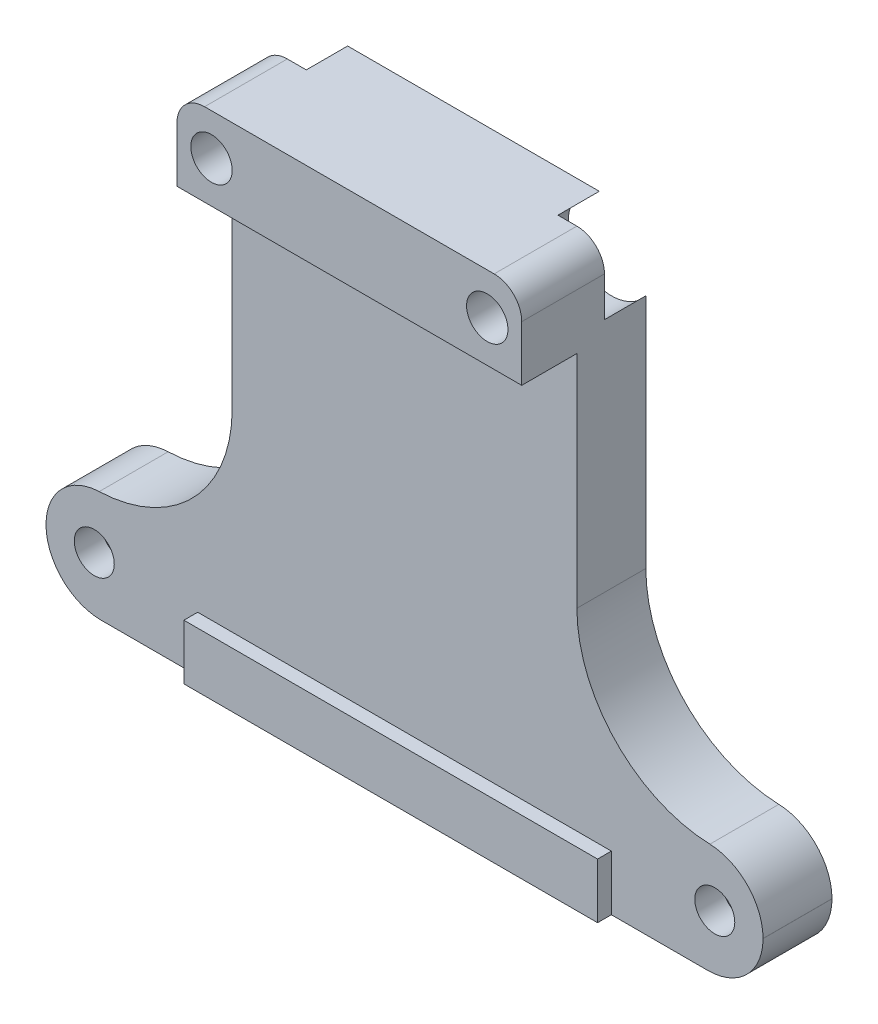
SolidWorks part; units mm, degrees
ref_plane "Спереди" through (0, 0, 0) normal (0, 0, 1) x (1, 0, 0)
ref_plane "Сверху" through (0, 0, 0) normal (0, 1, 0) x (1, 0, 0)
ref_plane "Справа" through (0, 0, 0) normal (1, 0, 0) x (0, 0, -1)
sketch "Эскиз1" plane through (0, 0, 0) normal (0, 0, 1) x (1, 0, 0)
  line L0 (-1000, 0) -> (49000, 0) construction
  line L1 (-26, -4) -> (26, -4)
  line L2 (-26, -4) -> (-26, 4)
  line L3 (-26, 4) -> (26, 4)
  line L4 (26, -4) -> (26, 4)
  line L5 (-26, -4) -> (26, 4) construction
  line L6 (-26, 4) -> (26, -4) construction
  circle A0 centre (-22.5, 0) radius 1.45
  circle A1 centre (22.5, 0) radius 1.45
  point P0 (0, 0)
  dimension "D2" = 2.9
  dimension "D1" = 8
  dimension "D3" = 45
  dimension "D4" = 22.5
  dimension "D5" = 52
extrude "Бобышка-Вытянуть1" add sketch "Эскиз1" along normal blind 5
sketch "Эскиз2" plane through (0, 0, 0) normal (0, 0, -1) x (-1, 0, 0)
  line L0 (-26, 4) -> (26, 4) construction
  line L1 (-12.5, 4) -> (12.5, 4)
  line L2 (-12.5, 4) -> (-12.5, 36)
  line L3 (-12.5, 36) -> (12.5, 36)
  line L4 (12.5, 4) -> (12.5, 36)
  line L5 (-12.5, 4) -> (12.5, 36) construction
  line L6 (-12.5, 36) -> (12.5, 4) construction
  line L7 (-1006.5256, 33) -> (48993.4744, 33) construction
  line L8 (0, -1000) -> (0, 49000) construction
  circle A0 centre (-10, 33) radius 1.5
  circle A1 centre (10, 33) radius 1.5
  point P4 (0, 20)
  dimension "D1" = 20
  dimension "D3" = 3
  dimension "D2" = 10
  dimension "D4" = 25
  dimension "D5" = 3
  dimension "D6" = 32
extrude "Бобышка-Вытянуть2" add sketch "Эскиз2" against normal blind 5
sketch "Эскиз3" plane through (0, 0, 5) normal (0, 0, -1) x (-1, 0, 0)
  line L0 (12.5, 4) -> (12.5, 36) construction
  line L1 (-12.5, 36) -> (12.5, 36)
  line L2 (-12.5, 36) -> (-12.5, 30)
  line L3 (-12.5, 30) -> (12.5, 30)
  line L4 (12.5, 36) -> (12.5, 30)
  line L5 (-12.5, 36) -> (12.5, 30) construction
  line L6 (-12.5, 30) -> (12.5, 36) construction
  circle A0 centre (10, 33) radius 1.5 construction
  circle A1 centre (-10, 33) radius 1.5 construction
  circle A2 centre (10, 33) radius 1.5
  circle A3 centre (-10, 33) radius 1.5
  point P4 (0, 33)
  dimension "D1" = 6
extrude "Бобышка-Вытянуть3" add sketch "Эскиз3" against normal blind 4
fillet "Скругление1" radius 10 2 edges at (12.5, 4, 2.5) (-12.5, 4, 2.5)
fillet "Скругление2" radius 4 4 edges at (-26, -4, 2.5) (-26, 4, 2.5) (26, -4, 2.5) (26, 4, 2.5)
fillet "Скругление3" radius 2 2 edges at (12.5, 36, 4.5) (-12.5, 36, 4.5)
sketch "Эскиз4" plane through (0, 0, 0) normal (0, 0, -1) x (-1, 0, 0)
  circle A0 centre (-10, 33) radius 3.125
  circle A1 centre (10, 33) radius 3.125
  circle A2 centre (-22.5, 0) radius 3.125
  circle A3 centre (22.5, 0) radius 3.125
  dimension "D1" = 6.25
extrude "Вырез-Вытянуть3" cut sketch "Эскиз4" against normal blind 3
sketch "Эскиз5" plane through (0, 0, 5) normal (0, 0, 1) x (1, 0, 0)
  line L0 (-22, -4) -> (22, -4) construction
  line L1 (15, -4) -> (-15, -4)
  line L2 (15, -4) -> (15, 0)
  line L3 (15, 0) -> (-15, 0)
  line L4 (-15, -4) -> (-15, 0)
  line L5 (15, -4) -> (-15, 0) construction
  line L6 (15, 0) -> (-15, -4) construction
  line L7 (12.5, 30) -> (12.5, 14) construction
  line L8 (-12.5, 14) -> (-12.5, 30) construction
  point P4 (0, -2)
  dimension "D1" = 2.5
  dimension "D2" = 2.5
  dimension "D3" = 4
extrude "Бобышка-Вытянуть4" add sketch "Эскиз5" along normal blind 1
